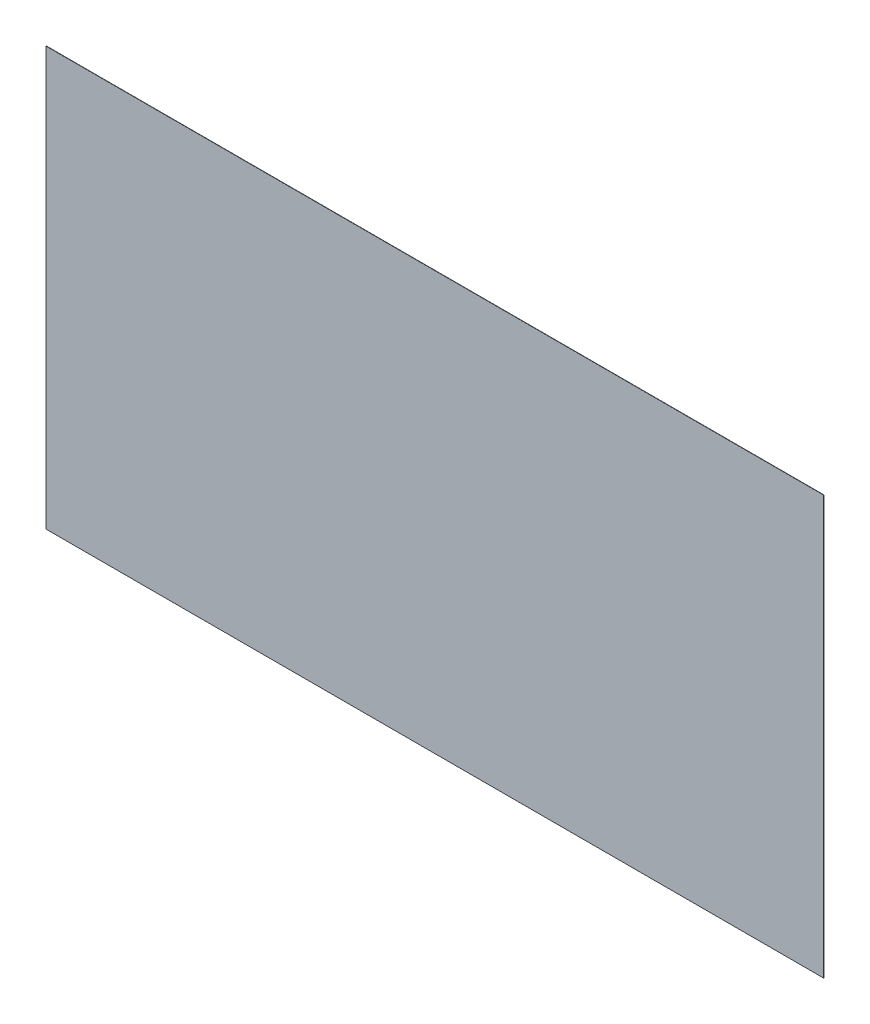
SolidWorks part; units mm, degrees
material "PVC 0.007 Plasticized"
ref_plane "Front Plane" through (0, 0, 0) normal (0, 0, 1) x (1, 0, 0)
ref_plane "Top Plane" through (0, 0, 0) normal (0, 1, 0) x (1, 0, 0)
ref_plane "Right Plane" through (0, 0, 0) normal (1, 0, 0) x (0, 0, -1)
sketch "Sketch1" plane through (0, 0, 0) normal (0, 0, 1) x (1, 0, 0)
  line L1 (-1050, -565) -> (1050, -565)
  line L2 (-1050, -565) -> (-1050, 565)
  line L3 (-1050, 565) -> (1050, 565)
  line L4 (1050, -565) -> (1050, 565)
  line L5 (-1050, -565) -> (1050, 565) construction
  line L6 (-1050, 565) -> (1050, -565) construction
  point P0 (0, 0)
  dimension "D1" = 2100
  dimension "D2" = 1130
extrude "Boss-Extrude1" add sketch "Sketch1" along normal blind 0.9
shell "Shell1" thickness 0.35 removed face at (0, 565, 0.45)
